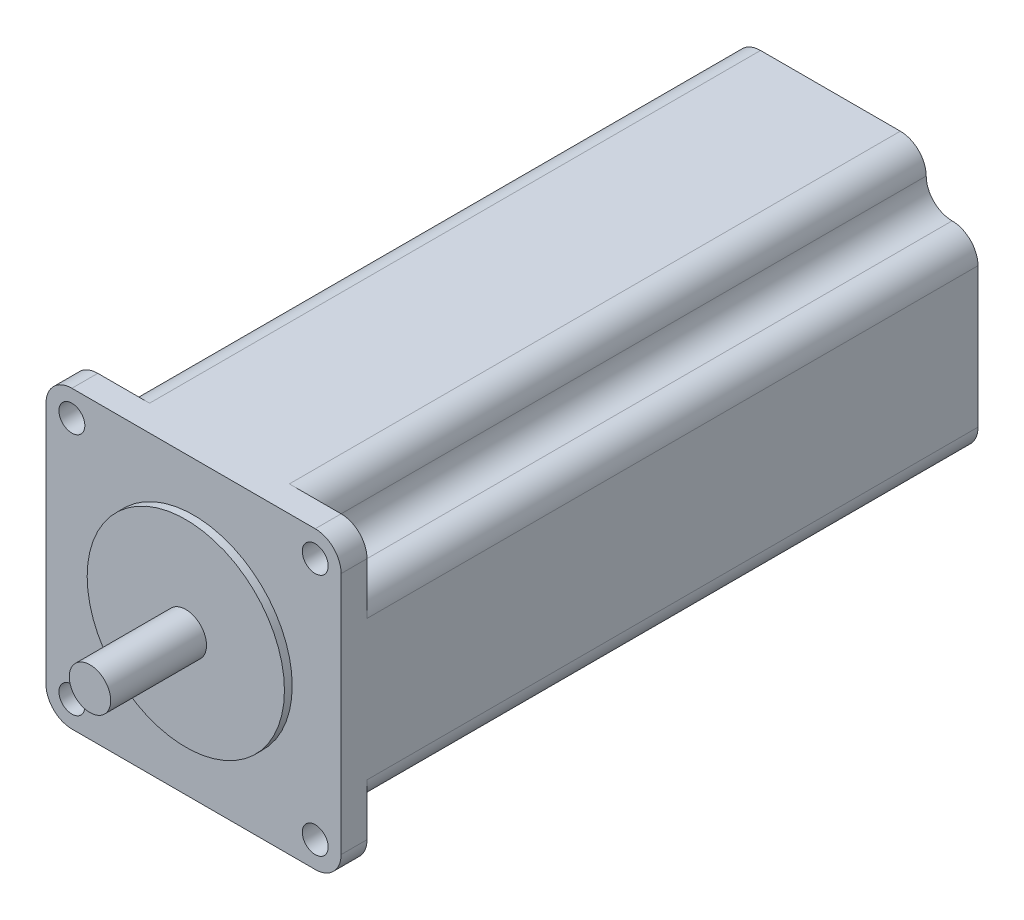
SolidWorks part; units mm, degrees
ref_plane "Front Plane" through (0, 0, 0) normal (0, 0, 1) x (1, 0, 0)
ref_plane "Top Plane" through (0, 0, 0) normal (0, 1, 0) x (1, 0, 0)
ref_plane "Right Plane" through (0, 0, 0) normal (1, 0, 0) x (0, 0, -1)
sketch "Sketch1" plane through (0, 0, 0) normal (0, 0, 1) x (1, 0, 0)
  line L1 (-33.3612, 31.2642) -> (23.6388, 31.2642)
  line L2 (-33.3612, 31.2642) -> (-33.3612, -25.7358)
  line L3 (-33.3612, -25.7358) -> (23.6388, -25.7358)
  line L4 (23.6388, 31.2642) -> (23.6388, -25.7358)
  dimension "D1" = 57
  dimension "D2" = 57
extrude "Boss-Extrude1" add sketch "Sketch1" along normal blind 123
sketch "Sketch2" plane through (0, 0, 0) normal (0, 0, -1) x (-1, 0, 0)
  line L1 (-23.6388, 31.2642) -> (-13.6388, 31.2642)
  line L2 (-23.6388, 31.2642) -> (-23.6388, 21.2642)
  line L3 (-23.6388, 21.2642) -> (-13.6388, 21.2642)
  line L4 (-13.6388, 31.2642) -> (-13.6388, 21.2642)
  dimension "D1" = 10
  dimension "D2" = 10
extrude "Cut-Extrude1" cut sketch "Sketch2" against normal blind 118
pattern_linear "LPattern1" count 2 spacing 47 along (-1, 0, 0) count 2 spacing 47 along (0, -1, 0) of "Cut-Extrude1"
sketch "Sketch3" plane through (0, 0, 123) normal (0, 0, 1) x (1, 0, 0)
  line L0 (23.6388, 31.2642) -> (-33.3612, 31.2642) construction
  line L1 (-33.3612, 31.2642) -> (-33.3612, -25.7358) construction
  circle A0 centre (-28.3612, 26.2642) radius 2.5
  dimension "D3" = 5
  dimension "D1" = 5
  dimension "D2" = 5
extrude "Cut-Extrude2" cut sketch "Sketch3" against normal blind 50
pattern_linear "LPattern2" count 2 spacing 47 along (1, 0, 0) count 2 spacing 47 along (0, -1, 0) of "Cut-Extrude2"
fillet "Fillet1" radius 5 16 edges at (-33.3612, 21.2642, 59) (-23.3612, 21.2642, 59) (-23.3612, 31.2642, 59) (13.6388, 31.2642, 59) (13.6388, 21.2642, 59) (23.6388, 21.2642, 59) (23.6388, -25.7358, 120.5) (23.6388, -15.7358, 59) (13.6388, -15.7358, 59) (13.6388, -25.7358, 59) (-23.3612, -25.7358, 59) (-23.3612, -15.7358, 59) (-33.3612, -15.7358, 59) (-33.3612, -25.7358, 120.5) (-33.3612, 31.2642, 120.5) (23.6388, 31.2642, 120.5)
sketch "Sketch5" plane through (0, 0, 123) normal (0, 0, 1) x (1, 0, 0)
  line L0 (18.6388, 31.2642) -> (-28.3612, 31.2642) construction
  line L1 (-33.3612, 26.2642) -> (-33.3612, -20.7358) construction
  circle A0 centre (-4.8612, 2.7642) radius 19.05
  dimension "D1" = 28.5
  dimension "D2" = 28.5
extrude "Boss-Extrude3" add sketch "Sketch5" along normal blind 1.5
sketch "Sketch4" plane through (0, 0, 123) normal (0, 0, 1) x (1, 0, 0)
  line L0 (18.6388, 31.2642) -> (-28.3612, 31.2642) construction
  line L1 (23.6388, -20.7358) -> (23.6388, 26.2642) construction
  circle A0 centre (-4.8612, 2.7642) radius 4
  dimension "D3" = 8
  dimension "D1" = 28.5
  dimension "D2" = 28.5
extrude "Boss-Extrude2" add sketch "Sketch4" along normal blind 20
